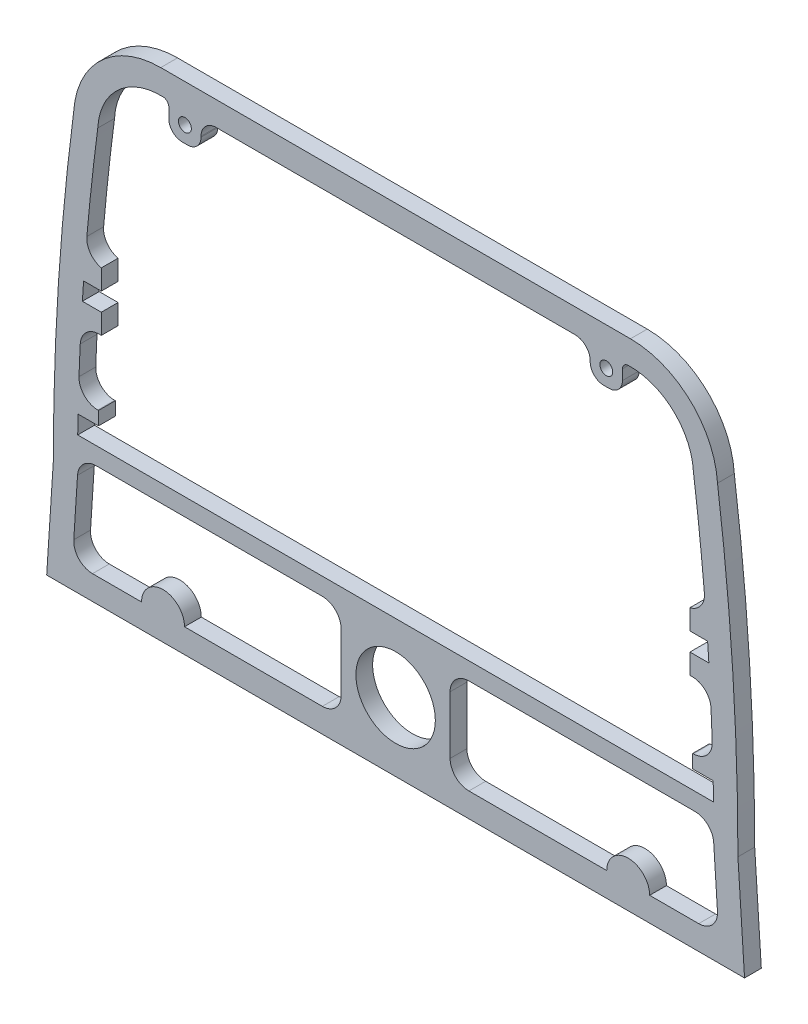
SolidWorks part; units mm, degrees
material "Delrin 2700 NC010, Low Viscosity Acetal Copolymer (SS)"
ref_plane "Front Plane" through (0, 0, 0) normal (0, 0, 1) x (1, 0, 0)
ref_plane "Top Plane" through (0, 0, 0) normal (0, 1, 0) x (1, 0, 0)
ref_plane "Right Plane" through (0, 0, 0) normal (1, 0, 0) x (0, 0, -1)
sketch "Sketch1" plane through (0, 0, 0) normal (0, 0, 1) x (1, 0, 0)
  line L0 (32.3937, -12.6084) -> (33.02, -22.225)
  line L1 (22.225, 24.765) -> (-22.225, 24.765)
  line L2 (-33.02, -22.225) -> (-30.4626, 17.0464) construction
  line L3 (-32.3937, -12.6084) -> (-32.3937, 14.6458) construction
  line L4 (-32.3937, -12.6084) -> (-33.02, -22.225)
  line L5 (16.9823, 22.479) -> (-16.9823, 22.479)
  line L6 (29.9931, -10.922) -> (30.5803, -19.939)
  line L7 (-30.5803, -19.939) -> (-24.0406, -19.939)
  line L8 (-33.02, -22.225) -> (33.02, -22.225)
  line L9 (-29.9931, -10.922) -> (-30.5803, -19.939)
  line L10 (-18.415, 21.0463) -> (-18.415, 20.955)
  line L11 (-19.685, 19.685) -> (-20.193, 19.685)
  line L12 (-21.463, 20.955) -> (-21.463, 21.9156)
  line L13 (18.415, 21.0463) -> (18.415, 20.955)
  line L14 (19.685, 19.685) -> (20.193, 19.685)
  line L15 (21.463, 20.955) -> (21.463, 21.9156)
  line L16 (30.0191, -6.2738) -> (28.1141, -6.2738)
  line L17 (28.1141, -6.2738) -> (28.1141, -7.5438)
  line L18 (0, 18.415) -> (0, -18.415) construction
  line L19 (-29.5244, 3.6322) -> (-27.8513, 3.6322)
  line L20 (28.1141, -7.5438) -> (30.0511, -7.5438)
  line L21 (-19.9766, -19.939) -> (-5.1562, -19.939)
  line L22 (22.225, 22.479) -> (-22.225, 22.479) construction
  line L23 (-30.1077, -12.6826) -> (-30.5803, -19.939) construction
  line L24 (29.7563, 0) -> (27.8513, 0)
  line L25 (27.8513, 0) -> (27.8513, 1.905)
  line L26 (27.8513, 1.905) -> (29.642, 1.905)
  line L27 (29.5244, 3.6322) -> (27.8513, 3.6322)
  line L28 (5.1562, -19.939) -> (19.9766, -19.939)
  line L29 (-30.5803, -19.939) -> (30.5803, -19.939) construction
  line L30 (24.0406, -19.939) -> (30.5803, -19.939)
  line L31 (30.1077, -12.6826) -> (30.5803, -19.939) construction
  line L32 (27.8513, 3.6322) -> (27.8513, 5.5372)
  line L33 (27.8513, 5.5372) -> (29.3793, 5.5372)
  line L34 (-30.0831, -9.271) -> (30.0831, -9.271)
  line L35 (-5.1562, -10.922) -> (-5.1562, -19.939)
  line L36 (-29.9931, -10.922) -> (-5.1562, -10.922)
  line L37 (5.1562, -10.922) -> (29.9931, -10.922)
  line L38 (-30.0831, -10.922) -> (30.0831, -10.922) construction
  line L39 (5.1562, -10.922) -> (5.1562, -19.939)
  line L40 (18.415, 21.209) -> (19.939, 21.209) construction
  line L41 (19.939, 21.209) -> (21.463, 21.209) construction
  line L42 (19.939, 21.209) -> (19.939, 19.685) construction
  line L43 (19.939, 19.685) -> (19.939, 20.5994) construction
  line L44 (-27.8513, 3.6322) -> (-27.8513, 5.5372)
  line L45 (-27.8513, 5.5372) -> (-29.3793, 5.5372)
  line L46 (-28.1141, -7.5438) -> (-30.0511, -7.5438)
  line L47 (-28.1141, -6.2738) -> (-28.1141, -7.5438)
  line L48 (-30.0191, -6.2738) -> (-28.1141, -6.2738)
  line L49 (-27.8513, 1.905) -> (-29.642, 1.905)
  line L50 (-27.8513, 0) -> (-27.8513, 1.905)
  line L51 (-29.7563, 0) -> (-27.8513, 0)
  arc A0 (22.225, 24.765) -> (30.4626, 17.0464) centre (22.225, 16.51) cw
  arc A1 (-22.225, 24.765) -> (-30.4626, 17.0464) centre (-22.225, 16.51) ccw
  arc A2 (32.3937, -12.6084) -> (30.4626, 17.0464) centre (-196.2574, -12.6084) ccw
  circle A3 centre (0, -15.748) radius 3.7592
  circle A4 centre (19.4575, -19.05) radius 0.5715
  arc A5 (-32.3937, -12.6084) -> (-30.4626, 17.0464) centre (196.2574, -12.6084) cw
  arc A6 (-30.1077, -12.6826) -> (-30.1077, -12.6084) centre (196.2574, -12.6084) cw
  arc A7 (-20.193, 19.685) -> (-21.463, 20.955) centre (-20.193, 20.955) cw
  arc A8 (30.0191, -6.2738) -> (29.7563, 0) centre (-196.2574, -12.6084) ccw
  circle A9 centre (-19.939, 21.209) radius 0.6096
  circle A10 centre (19.939, 21.209) radius 0.6096
  arc A11 (-24.0406, -19.939) -> (-19.9766, -19.939) centre (-22.0086, -19.939) cw
  circle A12 centre (-19.4575, -19.05) radius 0.5715
  arc A13 (24.0406, -19.939) -> (19.9766, -19.939) centre (22.0086, -19.939) ccw
  arc A14 (-18.415, 20.955) -> (-19.685, 19.685) centre (-19.685, 20.955) cw
  arc A15 (-16.9823, 22.479) -> (-18.415, 21.0463) centre (-16.9823, 21.0463) ccw
  arc A16 (-21.463, 21.9156) -> (-22.0016, 22.4748) centre (-22.0226, 21.9156) ccw
  arc A17 (16.9823, 22.479) -> (18.415, 21.0463) centre (16.9823, 21.0463) cw
  arc A18 (-22.0016, 22.4748) -> (-28.1854, 16.8295) centre (-22.225, 16.51) ccw
  arc A19 (22.0016, 22.4748) -> (28.1854, 16.8295) centre (22.225, 16.51) cw
  arc A20 (30.1077, -12.6826) -> (30.1077, -12.6084) centre (-196.2574, -12.6084) ccw
  arc A21 (18.415, 20.955) -> (19.685, 19.685) centre (19.685, 20.955) ccw
  arc A22 (20.193, 19.685) -> (21.463, 20.955) centre (20.193, 20.955) ccw
  arc A23 (21.463, 21.9156) -> (22.0016, 22.4748) centre (22.0226, 21.9156) cw
  arc A24 (29.3793, 5.5372) -> (28.1854, 16.8295) centre (-196.2574, -12.6084) ccw
  arc A25 (29.642, 1.905) -> (29.5244, 3.6322) centre (-196.2574, -12.6084) ccw
  arc A26 (-29.3793, 5.5372) -> (-28.1854, 16.8295) centre (196.2574, -12.6084) cw
  arc A27 (22.225, 22.479) -> (28.1854, 16.8295) centre (22.225, 16.51) cw construction
  arc A28 (-22.225, 22.479) -> (-28.1854, 16.8295) centre (-22.225, 16.51) ccw construction
  arc A29 (30.0831, -9.271) -> (30.0511, -7.5438) centre (-196.2574, -12.6084) ccw
  arc A30 (-30.1077, -12.6826) -> (-28.1854, 16.8295) centre (196.2574, -12.6084) cw construction
  arc A31 (-29.642, 1.905) -> (-29.5244, 3.6322) centre (196.2574, -12.6084) cw
  arc A32 (30.1077, -12.6826) -> (28.1854, 16.8295) centre (-196.2574, -12.6084) ccw construction
  arc A33 (-30.0831, -9.271) -> (-30.0511, -7.5438) centre (196.2574, -12.6084) cw
  arc A34 (-30.0191, -6.2738) -> (-29.7563, 0) centre (196.2574, -12.6084) cw
  point P0 (0, 0)
  point P1 (0, 24.765)
  point P26 (0, -22.225)
  point P104 (-3.7592, -15.748)
  dimension "D4" = 2.286
  dimension "D6" = 8.255
  dimension "D7" = 19.4575
  dimension "D8" = 46.99
  dimension "D9" = 6.477
  dimension "D5" = 1.2192
  dimension "D17" = 1.143
  dimension "D3" = 7.5184
  dimension "D18" = 2.032
  dimension "D19" = 1.27
  dimension "D20" = 1.27
  dimension "D31" = 0.5596
  dimension "D32" = 1.4327
  dimension "D2" = 44.45
  dimension "D10" = 3.175
  dimension "D11" = 1.27
  dimension "D12" = 66.04
  dimension "D13" = 19.939
  dimension "D14" = 10.668
  dimension "D15" = 5.1562
  dimension "D16" = 15.748
  dimension "D21" = 1.27
  dimension "D22" = 1.905
  dimension "D23" = 1.7272
  dimension "D24" = 2.4007
  dimension "D25" = 1.905
  dimension "D26" = 1.7272
  dimension "D27" = 11.176
  dimension "D28" = 1.651
  dimension "D30" = 0.508
extrude "Boss-Extrude1" add sketch "Sketch1" along normal blind 1.5875 contours A20 | A6 | A6 | A20 | A5 L4 L8 L0 A2 A0 L1 A1 A29 L34 A18 A16 L12 A7 L11 A14 L10 A15 L5 A17 L13 A21 L14 A22 L15 A23 A19 A24 L33 L32 L27 A25 L26 L25 L24 A8 L16 L17 L20 A12 A11 L7 L9 L36 region at (31.8981, -17.4694, 0)
ref_axis "Axis1" through (0, -15.748, 0) along (0, 0, 1)
fillet "Fillet1" radius 1.778 14 edges at (-30.0191, -6.2738, 0.7937) (-29.7563, 0, 0.7937) (-29.3793, 5.5372, 0.7937) (29.7563, 0, 0.7937) (29.3793, 5.5372, 0.7937) (30.0191, -6.2738, 0.7937) (-5.1562, -19.939, 0.7937) (-29.9931, -10.922, 0.7937) (-30.5803, -19.939, 0.7937) (-5.1562, -10.922, 0.7937) (30.5803, -19.939, 0.7937) (5.1562, -19.939, 0.7937) (5.1562, -10.922, 0.7937) (29.9931, -10.922, 0.7937)
